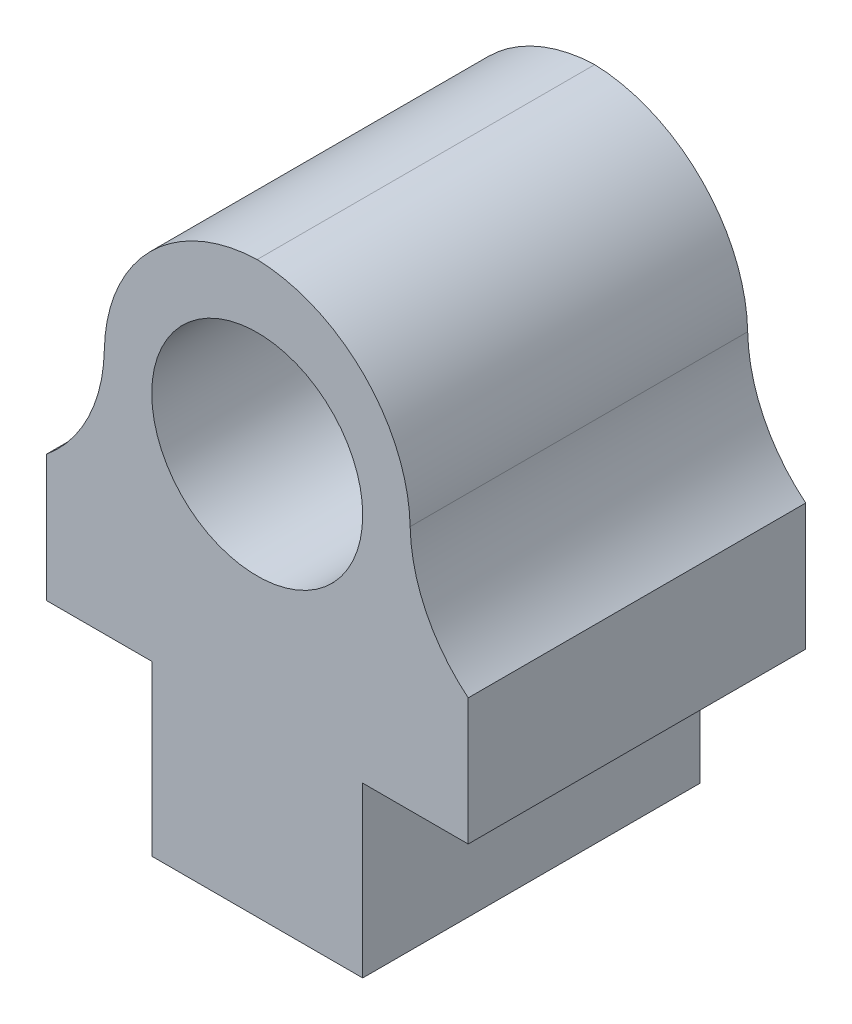
SolidWorks part; units mm, degrees
ref_plane "Front Plane" through (0, 0, 0) normal (0, 0, 1) x (1, 0, 0)
ref_plane "Top Plane" through (0, 0, 0) normal (0, 1, 0) x (1, 0, 0)
ref_plane "Right Plane" through (0, 0, 0) normal (1, 0, 0) x (0, 0, -1)
sketch "Sketch6" plane through (0, 0, 0) normal (0, 1, 0) x (1, 0, 0)
  line L1 (0, 0) -> (20, 0)
  line L2 (0, 0) -> (0, 16)
  line L3 (0, 16) -> (20, 16)
  line L4 (20, 0) -> (20, 16)
  dimension "D1" = 20
  dimension "D2" = 16
extrude "Boss-Extrude5" add sketch "Sketch6" along normal blind 6
sketch "Sketch7" plane through (0, 0, 0) normal (0, -1, 0) x (1, 0, 0)
  line L0 (0, 0) -> (20, 0) construction
  line L1 (5, 0) -> (15, 0)
  line L2 (5, 0) -> (5, -16)
  line L3 (5, -16) -> (15, -16)
  line L4 (15, 0) -> (15, -16)
  line L5 (20, -16) -> (0, -16) construction
  line L6 (0, -16) -> (0, 0) construction
  dimension "D1" = 10
  dimension "D2" = 5
extrude "Boss-Extrude6" add sketch "Sketch7" along normal blind 8
sketch "Sketch8" plane through (0, 6, 0) normal (0, 1, 0) x (1, 0, 0)
  line L0 (20, 16) -> (0, 16) construction
  line L1 (0, 0) -> (20, 0) construction
  line L2 (2.75, 16) -> (17.25, 16)
  line L3 (2.75, 16) -> (2.75, 0)
  line L4 (2.75, 0) -> (17.25, 0)
  line L5 (17.25, 16) -> (17.25, 0)
  line L6 (0, 16) -> (0, 0) construction
  dimension "D1" = 14.5
  dimension "D2" = 2.75
extrude "Boss-Extrude7" add sketch "Sketch8" along normal blind 13
sketch "Sketch9" plane through (0, 0, 0) normal (0, 0, 1) x (1, 0, 0)
  line L0 (2.75, 19) -> (2.75, 6) construction
  line L1 (2.75, 19) -> (17.25, 19) construction
  circle A0 centre (10, 11) radius 5
  dimension "D1" = 7.25
  dimension "D2" = 8
extrude "Cut-Extrude1" cut sketch "Sketch9" against normal through all
fillet "Fillet1" radius 7.5 2 edges at (17.25, 19, -8) (2.75, 19, -8)
fillet "Fillet2" radius 7.5 2 edges at (17.25, 6, -8) (2.75, 6, -8)
